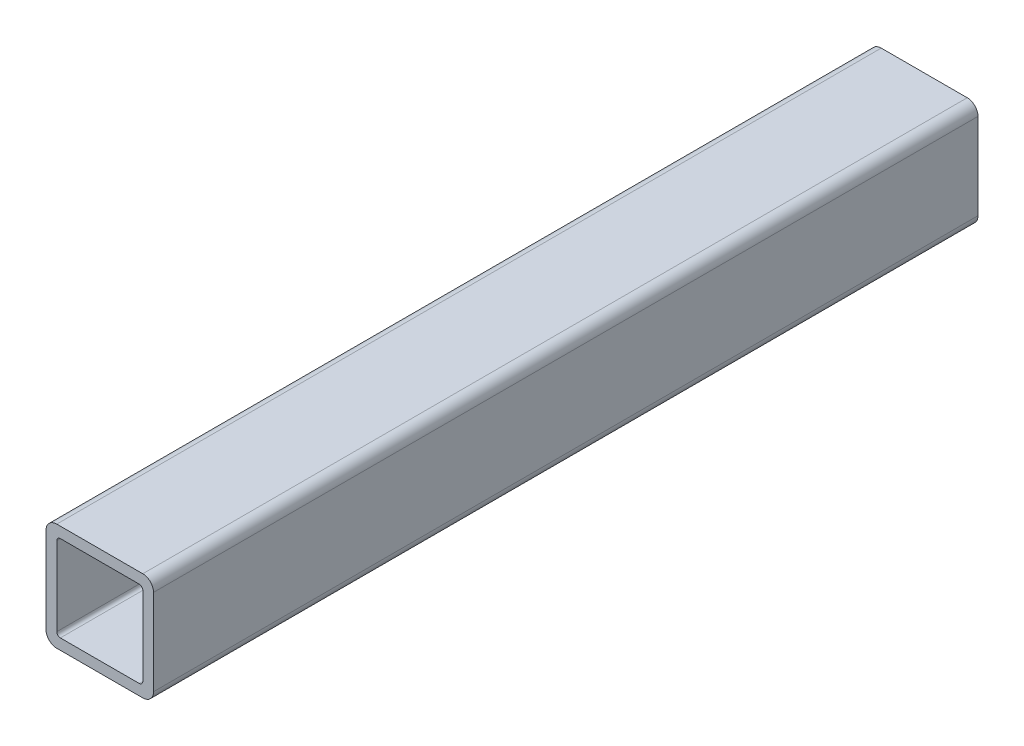
SolidWorks part; units mm, degrees
material "1.0553 (S355J0)"
ref_plane "Płaszczyzna przednia" through (0, 0, 0) normal (0, 0, 1) x (1, 0, 0)
ref_plane "Płaszczyzna górna" through (0, 0, 0) normal (0, 1, 0) x (1, 0, 0)
ref_plane "Płaszczyzna prawa" through (0, 0, 0) normal (1, 0, 0) x (0, 0, -1)
sketch "Szkic1" plane through (0, 0, 0) normal (0, 0, 1) x (1, 0, 0)
  line L0 (0, -55) -> (0, 55) construction
  line L1 (-12, -15) -> (12, -15)
  line L2 (-15, -12) -> (-15, 12)
  line L3 (-12, 15) -> (12, 15)
  line L4 (15, -12) -> (15, 12)
  line L5 (-11, -12) -> (11, -12)
  line L6 (-12, -11) -> (-12, 11)
  line L7 (-11, 12) -> (11, 12)
  line L8 (12, -11) -> (12, 11)
  line L10 (55, 0) -> (-55, 0) construction
  arc A0 (-12, -15) -> (-15, -12) centre (-12, -12) cw
  arc A1 (-15, 12) -> (-12, 15) centre (-12, 12) cw
  arc A2 (12, 15) -> (15, 12) centre (12, 12) cw
  arc A3 (15, -12) -> (12, -15) centre (12, -12) cw
  arc A4 (-12, -11) -> (-11, -12) centre (-11, -11) ccw
  arc A5 (11, -12) -> (12, -11) centre (11, -11) ccw
  arc A6 (12, 11) -> (11, 12) centre (11, 11) ccw
  arc A7 (-11, 12) -> (-12, 11) centre (-11, 11) ccw
  point P11 (0, 0)
  point P28 (0, -15)
  point P31 (-15, 0)
  dimension "D7" = 3
  dimension "D8" = 1
  dimension "D1" = 30
  dimension "D2" = 30
  dimension "D3" = 3
  dimension "D4" = 3
  dimension "D5" = 3
  dimension "D6" = 3
extrude "Dodanie-wyciągnięcie1" add sketch "Szkic1" along normal blind 230
sketch "Szkic4" [suppressed] plane through (0, 0, 0) normal (1, 0, 0) x (0, 0, -1)
  line L0 (-119.2, 0) -> (0, 0) construction
  line L1 (-119.2, -12) -> (-119.2, 12) construction
  circle A0 centre (-59.6, 0) radius 5
  dimension "D1" = 10
extrude "Wytnij-wyciągnięcie3" [suppressed] cut sketch "Szkic4" along normal blind 29 and the other way blind 45
sketch "Szkic2" [suppressed] plane through (0, 0, 0) normal (1, 0, 0) x (0, 0, -1)
  line L4 (-1260, -15) -> (0, -15) construction
  line L6 (-1260, 15) -> (-1260, -15)
  line L7 (-1260, -15) -> (-420, -15)
  line L9 (-420, -15) -> (-402.6795, 15)
  line L10 (-1260, 15) -> (0, 15) construction
  line L11 (-402.6795, 15) -> (-1260, 15)
  line L12 (-17.3205, -15) -> (0, 15)
  line L14 (0, 15) -> (0, -15)
  line L15 (0, -15) -> (-17.3205, -15)
  dimension "D1" = 60
  dimension "D2" = 420
extrude "Wytnij-wyciągnięcie1" [suppressed] cut sketch "Szkic2" against normal blind 72 and the other way blind 88
sketch "Szkic3" [suppressed] plane through (0, 0, 0) normal (1, 0, 0) x (0, 0, -1)
  line L0 (-320, 15) -> (-320, -15) construction
  line L1 (-640, 15) -> (0, 15) construction
  line L2 (-640, -15) -> (0, -15) construction
  line L3 (-640, 0) -> (0, 0) construction
  line L4 (-640, -12) -> (-640, 12) construction
  circle A0 centre (-390, 0) radius 5
  circle A1 centre (-250, 0) radius 5
  dimension "D2" = 10
  dimension "D1" = 140
extrude "Wytnij-wyciągnięcie2" [suppressed] cut sketch "Szkic3" along normal blind 42 and the other way blind 37
sketch "Szkic5" [suppressed] plane through (-15, 0, 0) normal (-1, 0, 0) x (0, 0, 1)
  line L1 (185, 12) -> (185, -12) construction
  circle A0 centre (20, 0) radius 6.25
  circle A1 centre (140, 0) radius 6.25
  dimension "D3" = 12.5
  dimension "D1" = 120
  dimension "D4" = 45
extrude "Wytnij-wyciągnięcie4" [suppressed] cut sketch "Szkic5" against normal up to surface (30 mm away) up to face at (15, 0, 115)
